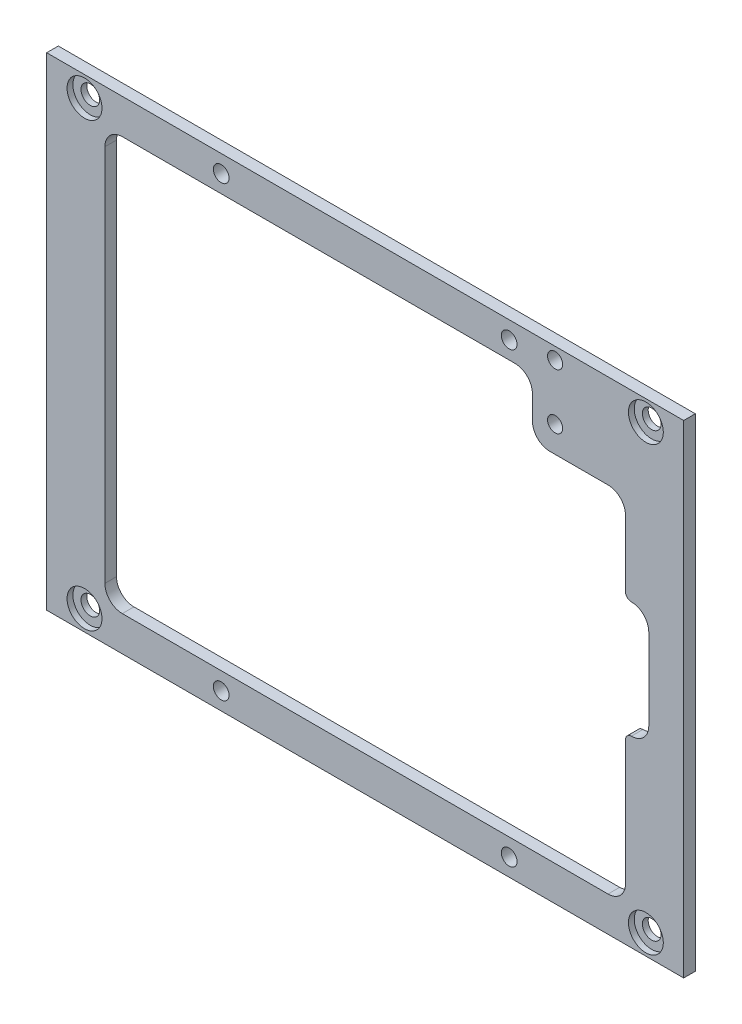
SolidWorks part; units mm, degrees
ref_plane "Front Plane" through (0, 0, 0) normal (0, 0, 1) x (1, 0, 0)
ref_plane "Top Plane" through (0, 0, 0) normal (0, 1, 0) x (1, 0, 0)
ref_plane "Right Plane" through (0, 0, 0) normal (1, 0, 0) x (0, 0, -1)
sketch "Sketch1" plane through (0, 0, 0) normal (0, 0, 1) x (1, 0, 0)
  line L0 (55.75, -83) -> (-55.75, -83) construction
  line L1 (-54.75, 0) -> (54.75, 0)
  line L2 (-54.75, 0) -> (-54.75, -83)
  line L3 (-54.75, -83) -> (54.75, -83)
  line L4 (54.75, 0) -> (54.75, -83)
  line L6 (28.75, -9) -> (28.75, -13.1)
  line L7 (-41.75, -6) -> (25.75, -6)
  line L8 (-44.75, -9) -> (-44.75, -74)
  line L9 (-41.75, -77) -> (41.75, -77)
  line L10 (44.75, -19.1) -> (44.75, -31.5)
  line L11 (31.75, -16.1) -> (41.75, -16.1)
  line L12 (54.75, -41.5) -> (48.75, -41.5) construction
  line L13 (48.75, -41.5) -> (48.75, -51.5)
  line L14 (44.75, -31.5) -> (48.75, -31.5)
  line L16 (44.75, -51.5) -> (48.75, -51.5)
  line L17 (48.75, -31.5) -> (48.75, -41.5)
  line L18 (44.75, -51.5) -> (44.75, -74)
  arc A0 (41.75, -77) -> (44.75, -74) centre (41.75, -74) ccw
  arc A1 (-44.75, -74) -> (-41.75, -77) centre (-41.75, -74) ccw
  arc A2 (-41.75, -6) -> (-44.75, -9) centre (-41.75, -9) ccw
  arc A3 (28.75, -9) -> (25.75, -6) centre (25.75, -9) ccw
  arc A4 (41.75, -16.1) -> (44.75, -19.1) centre (41.75, -19.1) cw
  arc A5 (28.75, -13.1) -> (31.75, -16.1) centre (31.75, -13.1) ccw
  point P24 (28.75, -6)
  point P29 (28.75, -16.1)
  dimension "D6" = 3
  dimension "D8" = 3
  dimension "D2" = 10
  dimension "D3" = 10
  dimension "D4" = 6
  dimension "D5" = 6
  dimension "D7" = 73.5
  dimension "D9" = 16.1
  dimension "D10" = 4
  dimension "D11" = 10
  dimension "D12" = 10
  dimension "D13" = 89.5
  dimension "D14" = 83
extrude "Boss-Extrude1" add sketch "Sketch1" along normal blind 2
hole_wizard "Ø3.2 (3.2) Diameter Hole2" positions "Sketch4" profile "Sketch3" hole size "Ø3.2" standard "Ansi Metric" end condition up to next
sketch "Sketch4" plane through (0, 0, 2) normal (0, 0, 1) x (1, 0, 0)
  line L0 (-54.75, 0) -> (-54.75, -83) construction
  line L1 (54.75, 0) -> (-54.75, 0) construction
  line L2 (-54.75, -83) -> (54.75, -83) construction
  line L3 (54.75, -83) -> (54.75, 0) construction
  point P0 (-48.25, -3.5)
  point P1 (-48.25, -79.5)
  point P3 (48.25, -79.5)
  point P5 (48.25, -3.5)
  dimension "D1" = 6.5
  dimension "D2" = 3.5
  dimension "D3" = 6.5
  dimension "D4" = 3.5
  dimension "D5" = 3.5
  dimension "D6" = 6.5
  dimension "D7" = 6.5
  dimension "D8" = 3.5
sketch "Sketch3" plane through (-48.25, -3.5, 2) normal (1, 0, 0) x (0, -1, 0)
  line L0 (0, 0) -> (0, 2)
  line L1 (0, 2) -> (1.6, 2)
  line L2 (1.6, 2) -> (1.6, 0)
  line L5 (1.6, 0) -> (0, 0)
  line L11 (0, -6.35) -> (0, 107.95) construction
  dimension "Thru Hole Dia." = 3.2
  dimension "Thru Hole Depth" = 2
hole_wizard "Ø2.6 (2.6) Diameter Hole2" positions "Sketch6" profile "Sketch5" hole size "Ø2.6" standard "Ansi Metric" end condition up to next
sketch "Sketch6" plane through (0, 0, 2) normal (0, 0, 1) x (1, 0, 0)
  line L0 (28.75, -13.1) -> (28.75, -9) construction
  line L1 (41.75, -16.1) -> (31.75, -16.1) construction
  point P0 (32.65, -11.6)
  dimension "D1" = 3.9
  dimension "D2" = 4.5
sketch "Sketch5" plane through (32.65, -11.6, 2) normal (1, 0, 0) x (0, -1, 0)
  line L0 (0, 0) -> (0, 2)
  line L1 (0, 2) -> (1.3, 2)
  line L2 (1.3, 2) -> (1.3, 0)
  line L5 (1.3, 0) -> (0, 0)
  line L11 (0, -6.35) -> (0, 107.95) construction
  dimension "Thru Hole Dia." = 2.6
  dimension "Thru Hole Depth" = 2
hole_wizard "Ø2.6 (2.6) Diameter Hole1" positions "Sketch8" profile "Sketch7" hole size "Ø2.6" standard "Ansi Metric" end condition up to next
sketch "Sketch8" plane through (0, 0, 2) normal (0, 0, 1) x (1, 0, 0)
  line L0 (28.75, -13.1) -> (28.75, -9) construction
  circle A2 centre (32.65, -11.6) radius 1.3 construction
  point P0 (32.65, -2.07)
  dimension "D2" = 9.53
  dimension "D1" = 3.9
sketch "Sketch7" plane through (32.65, -2.07, 2) normal (1, 0, 0) x (0, -1, 0)
  line L0 (0, 0) -> (0, 2)
  line L1 (0, 2) -> (1.3, 2)
  line L2 (1.3, 2) -> (1.3, 0)
  line L5 (1.3, 0) -> (0, 0)
  line L11 (0, -6.35) -> (0, 107.95) construction
  dimension "Thru Hole Dia." = 2.6
  dimension "Thru Hole Depth" = 2
sketch "Sketch9" plane through (0, 0, 2) normal (0, 0, 1) x (1, 0, 0)
  circle A0 centre (-48.25, -3.5) radius 3
  circle A1 centre (48.25, -3.5) radius 3
  circle A2 centre (48.25, -79.5) radius 3
  circle A3 centre (-48.25, -79.5) radius 3
  dimension "D1" = 6
  dimension "D2" = 6
  dimension "D3" = 6
  dimension "D4" = 6
extrude "Cut-Extrude1" cut sketch "Sketch9" against normal blind 1
hole_wizard "Ø2.7 (2.7) Diameter Hole1" positions "Sketch11" profile "Sketch10" hole size "Ø2.7" standard "Ansi Metric" end condition up to next
sketch "Sketch11" plane through (0, 0, 2) normal (0, 0, 1) x (1, 0, 0)
  line L0 (-54.75, 0) -> (-54.75, -83) construction
  line L1 (54.75, 0) -> (-54.75, 0) construction
  line L2 (54.75, -83) -> (54.75, 0) construction
  line L3 (-54.75, -83) -> (54.75, -83) construction
  point P0 (-24.75, -3)
  point P1 (24.75, -3)
  point P3 (-24.75, -80)
  point P5 (24.75, -80)
  dimension "D1" = 30
  dimension "D2" = 3
  dimension "D3" = 30
  dimension "D4" = 3
  dimension "D5" = 3
  dimension "D6" = 30
  dimension "D7" = 30
  dimension "D8" = 3
sketch "Sketch10" plane through (-24.75, -3, 2) normal (1, 0, 0) x (0, -1, 0)
  line L0 (0, 0) -> (0, 2)
  line L1 (0, 2) -> (1.35, 2)
  line L2 (1.35, 2) -> (1.35, 0)
  line L5 (1.35, 0) -> (0, 0)
  line L11 (0, -6.35) -> (0, 107.95) construction
  dimension "Thru Hole Dia." = 2.7
  dimension "Thru Hole Depth" = 2
fillet "Fillet1" radius 1 2 edges at (44.75, -51.5, 1) (44.75, -31.5, 1)
fillet "Fillet2" radius 3 2 edges at (48.75, -31.5, 1) (48.75, -51.5, 1)
